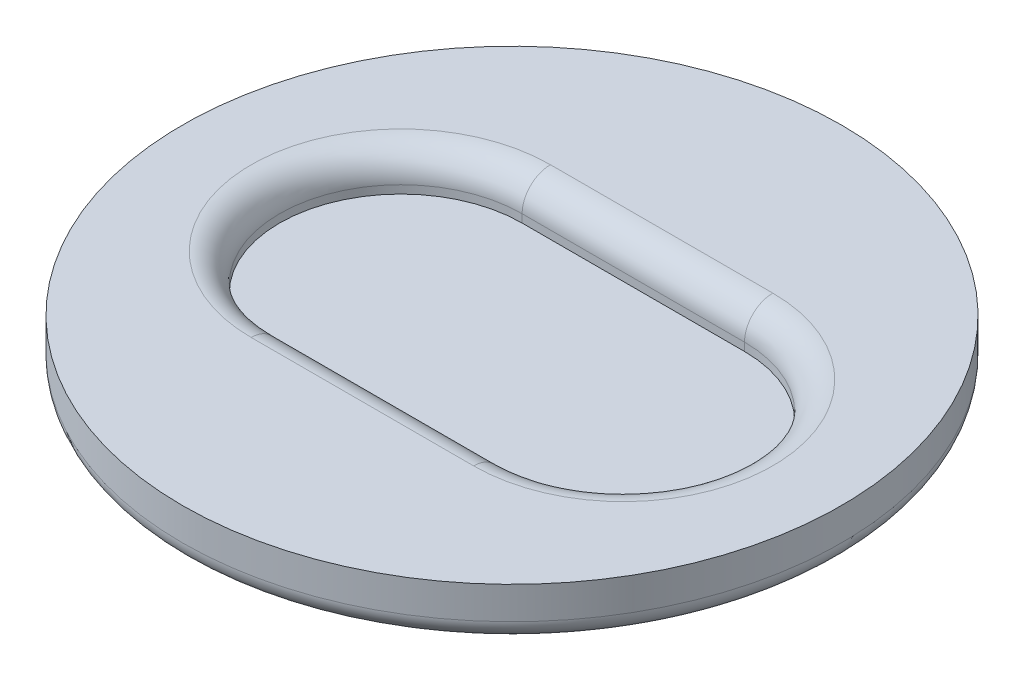
SolidWorks part; units mm, degrees
ref_plane "Front Plane" through (0, 0, 0) normal (0, 0, 1) x (1, 0, 0)
ref_plane "Top Plane" through (0, 0, 0) normal (0, 1, 0) x (1, 0, 0)
ref_plane "Right Plane" through (0, 0, 0) normal (1, 0, 0) x (0, 0, -1)
sketch "Sketch1" plane through (0, 0, 0) normal (0, 1, 0) x (1, 0, 0)
  line L0 (0, 0) -> (19.5381, 0) construction
  line L1 (0, 0) -> (-14.75, 0) construction
  line L2 (-2.75, 3) -> (2.75, 3)
  line L3 (-2.75, -3) -> (2.75, -3)
  circle A0 centre (0, 0) radius 8.15
  circle A3 centre (-2.75, 0) radius 3
  circle A4 centre (2.75, 0) radius 3
  dimension "D1" = 16.3
  dimension "D2" = 6
  dimension "D3" = 2.75
  dimension "D4" = 5.5
extrude "Boss-Extrude1" add sketch "Sketch1" along normal blind 1.3 contours A0 A4 L3 A3 L2 region at (-7.9195, 0, 0)
extrude "Boss-Extrude2" add sketch "Sketch1<3>" along normal blind 0.4 contours A4 A3 | A4 L2 A3 | A4 A3 | A3 A4 | A4 A3 L3 region at (-2.8307, 0, 0) region at (0, 0, -2.5063) region at (2.8307, 0, 0) region at (0, 0, 2.5063) region at (0, 0, 0)
sketch "Sketch1<3>" plane through (0, 0, 0) normal (0, 1, 0) x (1, 0, 0) same geometry as "Sketch1"
fillet "Fillet3" radius 0.7 4 edges at (5.75, 1.3, 0) (0, 1.3, 3) (-5.75, 1.3, 0) (0, 1.3, -3)
fillet "Fillet4" radius 0.5 1 edges at (0, 0, 8.15)
